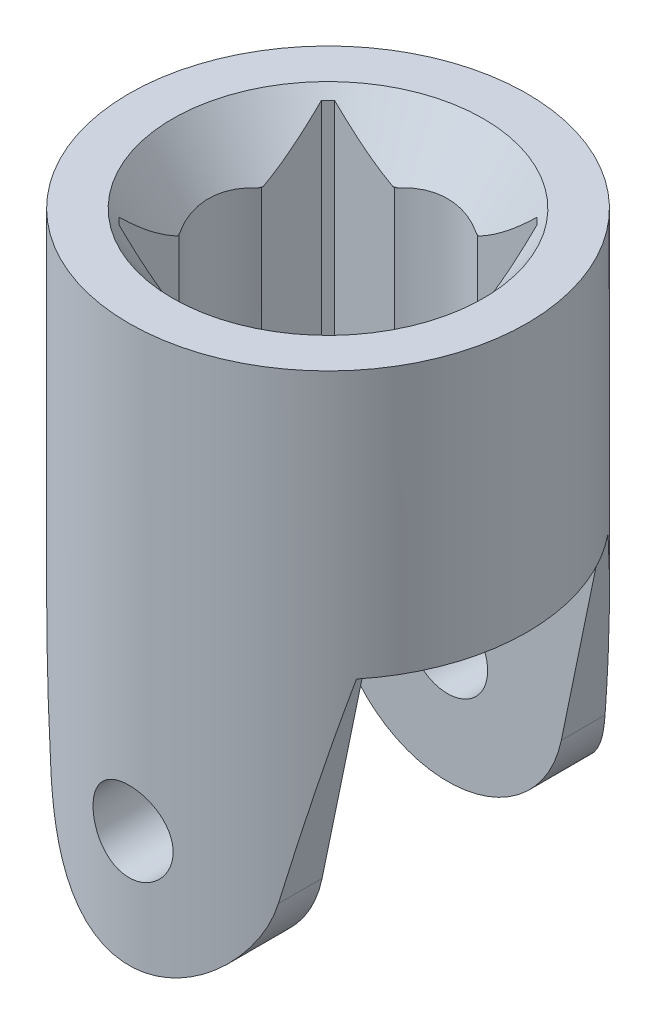
SolidWorks part; units mm, degrees
ref_plane "Front Plane" through (0, 0, 0) normal (0, 0, 1) x (1, 0, 0)
ref_plane "Top Plane" through (0, 0, 0) normal (0, 1, 0) x (1, 0, 0)
ref_plane "Right Plane" through (0, 0, 0) normal (1, 0, 0) x (0, 0, -1)
sketch "Sketch1" plane through (0, 0, 0) normal (0, 1, 0) x (1, 0, 0)
  circle A0 centre (0, 0) radius 12
  dimension "D1" = 24
extrude "Boss-Extrude1" add sketch "Sketch1" along normal blind 33.53
sketch "Sketch2" plane through (0, 33.53, 0) normal (0, 1, 0) x (1, 0, 0)
  line L0 (-6.5, 6.5) -> (-2.5, 6.5)
  line L1 (-6.5, 6.5) -> (6.5, 6.5) construction
  line L2 (-6.5, 6.5) -> (-6.5, -6.5) construction
  line L3 (-6.5, -6.5) -> (6.5, -6.5) construction
  line L4 (6.5, 6.5) -> (6.5, -6.5) construction
  line L5 (-6.5, 6.5) -> (6.5, -6.5) construction
  line L6 (-6.5, -6.5) -> (6.5, 6.5) construction
  line L7 (2.5, 6.5) -> (6.5, 6.5)
  line L8 (6.5, 6.5) -> (6.5, 2.5)
  line L9 (6.5, -2.5) -> (6.5, -6.5)
  line L10 (6.5, -6.5) -> (2.5, -6.5)
  line L11 (-2.5, -6.5) -> (-6.5, -6.5)
  line L12 (-6.5, -6.5) -> (-6.5, -2.5)
  line L13 (-6.5, 2.5) -> (-6.5, 6.5)
  arc A0 (-2.5, 6.5) -> (2.5, 6.5) centre (0, 2.4611) cw
  arc A1 (6.5, 2.5) -> (6.5, -2.5) centre (2.4611, 0) cw
  arc A2 (2.5, -6.5) -> (-2.5, -6.5) centre (0, -2.4611) cw
  arc A3 (-6.5, -2.5) -> (-6.5, 2.5) centre (-2.4611, 0) cw
  point P0 (0, 0)
  point P9 (0, 7.2111)
  point P28 (0, 0)
  dimension "D3" = 4.75
  dimension "D1" = 13
  dimension "D2" = 4
  dimension "D4" = 4
extrude "Cut-Extrude1" cut sketch "Sketch2" against normal blind 19.6
chamfer "Chamfer1" distance 0.4 angle 45 4 edges at (-6.5, 23.73, 6.5) (6.5, 23.73, 6.5) (-6.5, 23.73, -6.5) (6.5, 23.73, -6.5)
sketch "Sketch3" plane through (0, 33.53, 0) normal (0, 1, 0) x (1, 0, 0)
  circle A0 centre (0, 0) radius 9.375
  dimension "D1" = 18.75
extrude "Cut-Extrude2" cut sketch "Sketch3" against normal blind 3.4 draft 35
sketch "Sketch4" plane through (0, 0, 0) normal (0, -1, 0) x (1, 0, 0)
  line L1 (-12, 7.2111) -> (12, 7.2111)
  line L2 (-12, 7.2111) -> (-12, -7.2111)
  line L3 (-12, -7.2111) -> (12, -7.2111)
  line L4 (12, 7.2111) -> (12, -7.2111)
  arc A0 (2.5, 6.5) -> (-2.5, 6.5) centre (0, 2.4611) ccw construction
  arc A1 (-2.5, -6.5) -> (2.5, -6.5) centre (0, -2.4611) ccw construction
  circle A2 centre (0, 0) radius 12 construction
extrude "Cut-Extrude3" cut sketch "Sketch4" against normal blind 17.4
sketch "Sketch5" plane through (0, 0, 0) normal (0, 0, 1) x (1, 0, 0)
  line L0 (12, 17.4) -> (9.3, 17.4)
  line L1 (9.3, 17.4) -> (6.8548, 5.5817)
  line L2 (0, 0) -> (0, 33.53) construction
  line L3 (12, 33.53) -> (-12, 33.53) construction
  line L4 (-12, 17.4) -> (-9.3, 17.4)
  line L5 (-9.3, 17.4) -> (-6.8548, 5.5817)
  line L6 (-6.8548, 5.5817) -> (6.8548, 5.5817) construction
  line L7 (-12, 17.4) -> (-12, -3.1923)
  line L8 (-12, -3.1923) -> (12, -3.1923)
  line L9 (12, -3.1923) -> (12, 17.4)
  arc A0 (-6.8548, 5.5817) -> (6.8548, 5.5817) centre (0, 7) ccw
  circle A1 centre (0, 7) radius 2.415
  dimension "D1" = 7
  dimension "D3" = 4.83
  dimension "D2" = 2.7
extrude "Cut-Extrude4" cut sketch "Sketch5" against normal mid plane 67.4 contours A1 | A0 L5 L4 L7 L8 L9 L0 L1 region at (11.6838, 7.1039, 0) region at (0, 7, 0)
